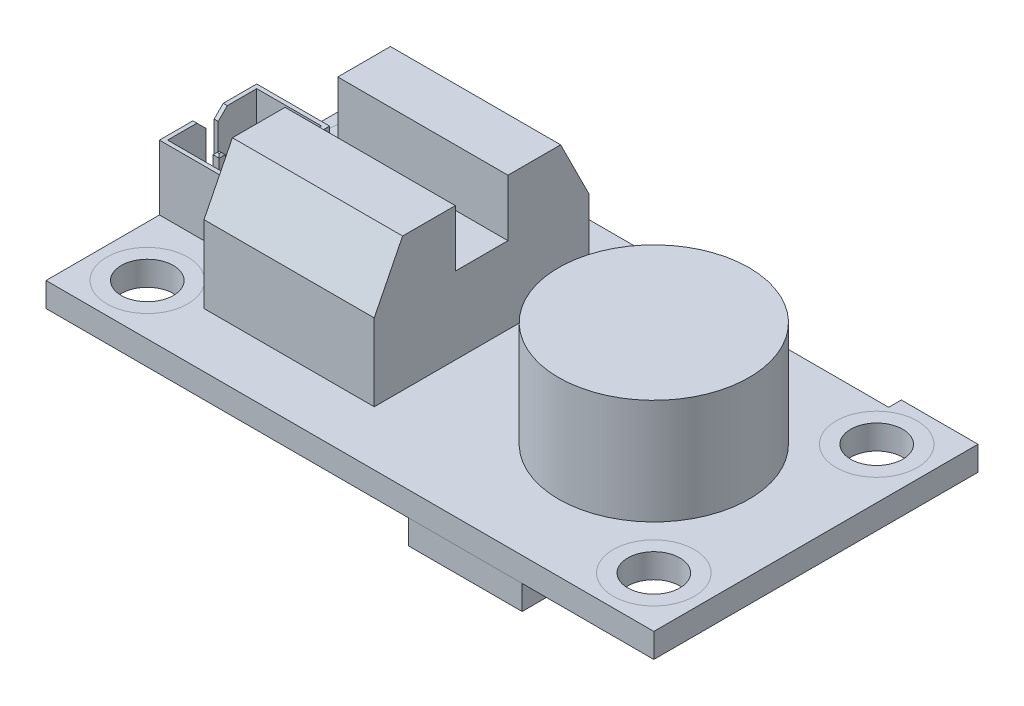
SolidWorks part; units mm, degrees
material "A-Glass Fiber"
ref_plane "Front Plane" through (0, 0, 0) normal (0, 0, 1) x (1, 0, 0)
ref_plane "Top Plane" through (0, 0, 0) normal (0, 1, 0) x (1, 0, 0)
ref_plane "Right Plane" through (0, 0, 0) normal (1, 0, 0) x (0, 0, -1)
sketch "Sketch1" plane through (0, 0, 0) normal (0, 1, 0) x (1, 0, 0)
  line L1 (19.05, -10.16) -> (-19.05, -10.16)
  line L2 (19.05, -10.16) -> (19.05, 10.16)
  line L3 (19.05, 10.16) -> (-19.05, 10.16)
  line L4 (-19.05, -10.16) -> (-19.05, 10.16)
  line L5 (19.05, -10.16) -> (-19.05, 10.16) construction
  line L6 (19.05, 10.16) -> (-19.05, -10.16) construction
  point P0 (0, 0)
  dimension "D1" = 38.1
  dimension "D2" = 20.32
extrude "Boss-Extrude1" add sketch "Sketch1" along normal blind 1.524
hole_wizard "#4 Clearance Hole1" positions "Sketch2" profile "Sketch3" hole size "#4" standard "ANSI Inch" end condition through all
sketch "Sketch2" plane through (0, 1.524, 0) normal (0, 1, 0) x (1, 0, 0)
  line L9 (-15.875, 6.985) -> (15.875, 6.985)
  line L10 (-15.875, 6.985) -> (-15.875, -6.985)
  line L11 (-15.875, -6.985) -> (15.875, -6.985)
  line L12 (15.875, 6.985) -> (15.875, -6.985)
  line L13 (19.05, -10.16) -> (19.05, 10.16) construction
  line L14 (19.05, 10.16) -> (-19.05, 10.16) construction
  line L15 (-19.05, 10.16) -> (-19.05, -10.16) construction
  line L16 (-19.05, -10.16) -> (19.05, -10.16) construction
  point P66 (-15.875, 6.985)
  point P67 (15.875, -6.985)
  point P70 (-15.875, -6.985)
  point P71 (15.875, 6.985)
  dimension "D1" = 3.175
  dimension "D2" = 3.175
  dimension "D3" = 3.175
  dimension "D4" = 3.175
sketch "Sketch3" plane through (-15.875, 1.524, -6.985) normal (1, 0, 0) x (0, 0, 1)
  line L0 (0, 0) -> (0, 1.524)
  line L1 (0, 1.524) -> (1.6319, 1.524)
  line L2 (1.6319, 1.524) -> (1.6319, 0)
  line L5 (1.6319, 0) -> (0, 0)
  line L11 (0, -6.35) -> (0, 107.95) construction
  dimension "Thru Hole Dia." = 3.2639
  dimension "Thru Hole Depth" = 1.524
sketch "Sketch4" plane through (0, 1.524, 0) normal (0, 1, 0) x (1, 0, 0)
  line L0 (-19.05, 10.16) -> (-19.05, -10.16) construction
  line L1 (-19.05, 3.048) -> (-14.478, 3.048)
  line L2 (-19.05, 3.048) -> (-19.05, -3.048)
  line L3 (-19.05, -3.048) -> (-14.478, -3.048)
  line L4 (-14.478, 3.048) -> (-14.478, -3.048)
  point P6 (-14.478, 0)
  dimension "D1" = 6.096
  dimension "D2" = 4.572
extrude "Boss-Extrude2" add sketch "Sketch4" along normal blind 4.064
sketch "Sketch5" plane through (0, 1.524, 0) normal (0, 1, 0) x (1, 0, 0)
  line L0 (19.05, -10.16) -> (19.05, 10.16) construction
  circle A0 centre (8.89, 0) radius 5.969
  dimension "D1" = 10.16
  dimension "D2" = 11.938
extrude "Boss-Extrude3" add sketch "Sketch5" along normal blind 6.604
sketch "Sketch6" plane through (0, 1.524, 0) normal (0, 1, 0) x (1, 0, 0)
  line L1 (-1.905, -6.731) -> (-12.573, -6.731)
  line L2 (-1.905, -6.731) -> (-1.905, 6.731)
  line L3 (-1.905, 6.731) -> (-12.573, 6.731)
  line L4 (-12.573, -6.731) -> (-12.573, 6.731)
  line L5 (-1.905, -6.731) -> (-12.573, 6.731) construction
  line L6 (-1.905, 6.731) -> (-12.573, -6.731) construction
  circle A1 centre (8.89, 0) radius 5.969 construction
  point P0 (-7.239, 0)
  dimension "D1" = 13.462
  dimension "D2" = 10.668
  dimension "D3" = 4.826
extrude "Boss-Extrude4" add sketch "Sketch6" along normal blind 4.826
sketch "Sketch7" plane through (-12.573, 0, 0) normal (-1, 0, 0) x (0, 0, 1)
  line L1 (-6.731, 6.35) -> (-4.953, 9.906)
  line L6 (0, 0) -> (0, 50000) construction
  line L18 (6.731, 6.35) -> (4.953, 9.906)
  line L19 (-4.953, 9.906) -> (-1.651, 9.906)
  line L20 (4.953, 9.906) -> (1.651, 9.906)
  line L21 (-1.651, 9.906) -> (-1.651, 6.35)
  line L22 (-6.731, 6.35) -> (6.731, 6.35) construction
  line L23 (1.651, 9.906) -> (1.651, 6.35)
  line L24 (-6.731, 6.35) -> (-1.651, 6.35)
  line L25 (6.731, 6.35) -> (1.651, 6.35)
  dimension "D1" = 3.556
  dimension "D2" = 3.302
  dimension "D3" = 3.302
extrude "Boss-Extrude5" add sketch "Sketch7" against normal up to surface (10.668 mm away) up to face at (-1.905, 3.937, 0)
sketch "Sketch8" plane through (0, 0, 0) normal (0, -1, 0) x (1, 0, 0)
  line L0 (19.05, -10.16) -> (-19.05, -10.16) construction
  line L1 (3.302, -10.16) -> (11.176, -10.16)
  line L2 (3.302, -10.16) -> (3.302, -4.572)
  line L3 (3.302, -4.572) -> (11.176, -4.572)
  line L4 (11.176, -10.16) -> (11.176, -4.572)
  line L5 (19.05, 10.16) -> (19.05, -10.16) construction
  dimension "D1" = 5.588
  dimension "D2" = 7.874
  dimension "D3" = 7.874
extrude "Boss-Extrude6" add sketch "Sketch8" along normal blind 3.048
sketch "Sketch9" plane through (0, 0, 0) normal (0, -1, 0) x (1, 0, 0)
  line L0 (-19.05, 10.16) -> (19.05, 10.16) construction
  line L1 (3.683, 10.16) -> (10.795, 10.16)
  line L2 (3.683, 10.16) -> (3.683, 5.08)
  line L3 (3.683, 5.08) -> (10.795, 5.08)
  line L4 (10.795, 10.16) -> (10.795, 5.08)
  line L5 (11.176, -4.572) -> (3.302, -4.572) construction
  point P8 (7.239, -4.572)
  point P9 (7.239, 5.08)
  dimension "D1" = 5.08
  dimension "D2" = 7.112
extrude "Boss-Extrude7" add sketch "Sketch9" along normal blind 1.524
sketch "Sketch10" plane through (0, 0, 0) normal (0, -1, 0) x (1, 0, 0)
  line L0 (10.795, 5.08) -> (10.795, 10.16) construction
  line L1 (14.859, 2.032) -> (12.319, 2.032)
  line L2 (14.859, 2.032) -> (14.859, -2.032)
  line L3 (14.859, -2.032) -> (12.319, -2.032)
  line L4 (12.319, 2.032) -> (12.319, -2.032)
  point P4 (14.859, 0)
  dimension "D1" = 4.064
  dimension "D2" = 2.54
  dimension "D3" = 1.524
extrude "Boss-Extrude8" add sketch "Sketch10" along normal blind 1.016
sketch "Sketch11" plane through (0, 0, 0) normal (0, -1, 0) x (1, 0, 0)
  line L0 (3.683, 10.16) -> (3.683, 5.08) construction
  line L1 (1.651, -2.54) -> (6.731, -2.54)
  line L2 (1.651, -2.54) -> (1.651, 2.54)
  line L3 (1.651, 2.54) -> (6.731, 2.54)
  line L4 (6.731, -2.54) -> (6.731, 2.54)
  line L5 (1.651, -2.54) -> (6.731, 2.54) construction
  line L6 (1.651, 2.54) -> (6.731, -2.54) construction
  point P0 (4.191, 0)
  dimension "D1" = 5.08
  dimension "D2" = 2.032
extrude "Boss-Extrude9" add sketch "Sketch11" along normal blind 1.016
sketch "Sketch12" plane through (0, 0, 0) normal (0, -1, 0) x (1, 0, 0)
  line L0 (-19.05, 10.16) -> (3.683, 10.16) construction
  line L1 (-0.381, 6.096) -> (-4.445, 6.096)
  line L2 (-0.381, 6.096) -> (-0.381, 8.128)
  line L3 (-0.381, 8.128) -> (-4.445, 8.128)
  line L4 (-4.445, 6.096) -> (-4.445, 8.128)
  line L5 (-0.381, 6.096) -> (-4.445, 8.128) construction
  line L6 (-0.381, 8.128) -> (-4.445, 6.096) construction
  line L7 (3.683, 10.16) -> (3.683, 5.08) construction
  point P0 (-2.413, 7.112)
  dimension "D1" = 2.032
  dimension "D2" = 4.064
  dimension "D3" = 2.032
  dimension "D4" = 4.064
extrude "Boss-Extrude10" add sketch "Sketch12" along normal blind 1.016
sketch "Sketch13" plane through (0, 0, 0) normal (0, -1, 0) x (1, 0, 0)
  line L0 (3.302, -4.572) -> (3.302, -10.16) construction
  line L1 (-2.286, -7.62) -> (-5.334, -7.62)
  line L2 (-2.286, -7.62) -> (-2.286, -4.572)
  line L3 (-2.286, -4.572) -> (-5.334, -4.572)
  line L4 (-5.334, -7.62) -> (-5.334, -4.572)
  line L5 (-2.286, -7.62) -> (-5.334, -4.572) construction
  line L6 (-2.286, -4.572) -> (-5.334, -7.62) construction
  line L7 (3.302, -10.16) -> (-19.05, -10.16) construction
  point P0 (-3.81, -6.096)
  dimension "D1" = 3.048
  dimension "D2" = 5.588
  dimension "D3" = 2.54
extrude "Boss-Extrude11" add sketch "Sketch13" along normal blind 0.508
sketch "Sketch14" plane through (0, 0, 0) normal (0, -1, 0) x (1, 0, 0)
  line L0 (-19.05, -10.16) -> (-19.05, 10.16) construction
  line L1 (-11.43, -4.572) -> (-8.382, -4.572)
  line L2 (-11.43, -4.572) -> (-11.43, -8.128)
  line L3 (-11.43, -8.128) -> (-8.382, -8.128)
  line L4 (-8.382, -4.572) -> (-8.382, -8.128)
  line L5 (-11.43, -4.572) -> (-8.382, -8.128) construction
  line L6 (-11.43, -8.128) -> (-8.382, -4.572) construction
  line L7 (3.302, -10.16) -> (-19.05, -10.16) construction
  point P0 (-9.906, -6.35)
  dimension "D1" = 3.556
  dimension "D2" = 3.048
  dimension "D3" = 7.62
  dimension "D4" = 2.032
extrude "Boss-Extrude12" add sketch "Sketch14" along normal blind 1.016
sketch "Sketch15" plane through (0, 0, 0) normal (0, -1, 0) x (1, 0, 0)
  line L0 (3.302, -10.16) -> (-19.05, -10.16) construction
  line L1 (-16.51, 3.302) -> (-14.478, 3.302)
  line L2 (-16.51, 3.302) -> (-16.51, -0.762)
  line L3 (-16.51, -0.762) -> (-14.478, -0.762)
  line L4 (-14.478, 3.302) -> (-14.478, -0.762)
  line L5 (-16.51, 3.302) -> (-14.478, -0.762) construction
  line L6 (-16.51, -0.762) -> (-14.478, 3.302) construction
  line L7 (-19.05, -10.16) -> (-19.05, 10.16) construction
  point P0 (-15.494, 1.27)
  dimension "D1" = 4.064
  dimension "D2" = 2.032
  dimension "D3" = 9.398
  dimension "D4" = 2.54
extrude "Boss-Extrude13" add sketch "Sketch15" along normal blind 1.524
sketch "Sketch16" plane through (0, 0, 0) normal (0, -1, 0) x (1, 0, 0)
  line L0 (-19.05, -10.16) -> (-19.05, 10.16) construction
  line L1 (-7.874, -1.524) -> (-10.922, -1.524)
  line L2 (-7.874, -1.524) -> (-7.874, 1.524)
  line L3 (-7.874, 1.524) -> (-10.922, 1.524)
  line L4 (-10.922, -1.524) -> (-10.922, 1.524)
  line L5 (-7.874, -1.524) -> (-10.922, 1.524) construction
  line L6 (-7.874, 1.524) -> (-10.922, -1.524) construction
  point P0 (-9.398, 0)
  point P8 (-19.05, 0)
  dimension "D1" = 3.048
  dimension "D2" = 8.128
extrude "Boss-Extrude14" add sketch "Sketch16" along normal blind 1.016
sketch "Sketch17" plane through (0, 0, 0) normal (0, -1, 0) x (1, 0, 0)
  line L0 (-19.05, -10.16) -> (-19.05, 10.16) construction
  line L1 (3.302, -10.16) -> (-19.05, -10.16) construction
  circle A0 centre (-11.684, -3.556) radius 0.508
  dimension "D1" = 1.016
  dimension "D2" = 6.858
  dimension "D3" = 6.096
extrude "Boss-Extrude15" add sketch "Sketch17" along normal blind 1.524
pattern_linear "LPattern1" count 4 spacing 2.794 along (1, 0, 0) of "Boss-Extrude15"
mirror "Mirror1" about plane through (0, 0, 0) normal (0, 0, 1) of "LPattern1"
sketch "Sketch22" plane through (0, 1.524, 0) normal (0, 1, 0) x (1, 0, 0)
  line L0 (19.05, 10.16) -> (-19.05, 10.16) construction
  line L1 (0.635, 10.16) -> (14.2431, 10.16)
  line L2 (0.635, 10.16) -> (0.635, 9.3663)
  line L3 (0.635, 9.3663) -> (14.2431, 9.3663)
  line L4 (14.2431, 10.16) -> (14.2431, 9.3663)
  line L5 (-1.905, 6.731) -> (-1.905, 4.953) construction
  circle A0 centre (15.875, 6.985) radius 1.6319 construction
  dimension "D1" = 0.7937
  dimension "D2" = 2.54
extrude "Cut-Extrude2" cut sketch "Sketch22" against normal up to surface (1.524 mm away) up to face at (-3.302, 0, 4.064)
sketch "Sketch18" plane through (-19.05, 0, 0) normal (-1, 0, 0) x (0, 0, 1)
  line L0 (-3.048, 1.524) -> (3.048, 1.524)
split line "Split Line1"
sketch "Sketch19" plane through (0, 0, 10.16) normal (0, 0, 1) x (1, 0, 0)
  line L0 (3.683, 0) -> (10.795, 0)
  line L1 (11.176, 0) -> (3.302, 0) construction
  line L2 (10.795, 0) -> (19.05, 0) construction
split line "Split Line2"
sketch "Sketch23" plane through (0, 1.524, 0) normal (0, 1, 0) x (1, 0, 0)
  circle A0 centre (-15.875, 6.985) radius 2.54
  circle A1 centre (15.875, 6.985) radius 2.54
  circle A2 centre (15.875, -6.985) radius 2.54
  circle A3 centre (-15.875, -6.985) radius 2.54
  dimension "D1" = 5.08
split line "Split Line3"
sketch "Sketch24" plane through (0, 5.588, 0) normal (0, 1, 0) x (1, 0, 0)
  line L8 (-18.796, 2.794) -> (-18.796, -2.794)
  line L9 (-18.796, -2.794) -> (-14.732, -2.794)
  line L10 (-14.732, -2.794) -> (-14.732, 2.794)
  line L11 (-14.732, 2.794) -> (-18.796, 2.794)
  line L12 (-18.796, 2.794) -> (-18.796, -2.794)
  line L13 (-18.796, -2.794) -> (-14.732, -2.794)
  line L14 (-14.732, -2.794) -> (-14.732, 2.794)
  line L15 (-14.732, 2.794) -> (-18.796, 2.794)
  dimension "D1" = 0.254
extrude "Cut-Extrude3" cut sketch "Sketch24" against normal offset from surface (3.556 mm away) 0.508 contours L12 L13 L14 L15 up to face at (15.875, 1.524, 9.525)
sketch "Sketch25" plane through (0, 2.032, 0) normal (0, 1, 0) x (1, 0, 0)
  line L0 (-17.018, 2.794) -> (-17.018, -2.794) construction
  line L1 (-14.732, 2.794) -> (-18.796, 2.794) construction
  line L2 (-14.732, -2.794) -> (-18.796, -2.794) construction
  line L3 (-18.796, 2.794) -> (-18.796, -2.794) construction
  line L4 (-17.018, 0) -> (-18.796, 0) construction
  line L5 (-16.8275, 1.143) -> (-17.2085, 1.143)
  line L6 (-16.8275, 1.143) -> (-16.8275, 1.524)
  line L7 (-16.8275, 1.524) -> (-17.2085, 1.524)
  line L8 (-17.2085, 1.143) -> (-17.2085, 1.524)
  line L9 (-16.8275, 1.143) -> (-17.2085, 1.524) construction
  line L10 (-16.8275, 1.524) -> (-17.2085, 1.143) construction
  line L11 (-16.8275, -1.524) -> (-17.2085, -1.524)
  line L12 (-16.8275, -1.524) -> (-16.8275, -1.143)
  line L13 (-16.8275, -1.143) -> (-17.2085, -1.143)
  line L14 (-17.2085, -1.524) -> (-17.2085, -1.143)
  line L15 (-16.8275, -1.524) -> (-17.2085, -1.143) construction
  line L16 (-16.8275, -1.143) -> (-17.2085, -1.524) construction
  line L17 (-18.796, -2.794) -> (-18.796, 2.794) construction
  point P8 (-17.018, 1.3335)
  point P13 (-17.018, -1.3335)
  dimension "D1" = 1.778
  dimension "D2" = 0.381
  dimension "D3" = 1.143
  dimension "D4" = 1.143
extrude "Boss-Extrude16" add sketch "Sketch25" along normal offset from surface (3.048 mm away) 0.508 up to face at (-16.764, 5.588, 0)
chamfer "Chamfer1" distance 0.127 angle 45 8 edges at (-16.8275, 5.08, 1.3335) (-17.018, 5.08, 1.524) (-17.2085, 5.08, 1.3335) (-17.018, 5.08, 1.143) (-16.8275, 5.08, -1.3335) (-17.018, 5.08, -1.143) (-17.2085, 5.08, -1.3335) (-17.018, 5.08, -1.524)
sketch "Sketch26" plane through (-19.05, 0, 0) normal (-1, 0, 0) x (0, 0, 1)
  line L0 (0, 5.588) -> (0, 1.524) construction
  line L1 (-3.048, 5.588) -> (3.048, 5.588) construction
  line L2 (-3.048, 1.524) -> (3.048, 1.524) construction
  line L3 (-0.9525, 5.588) -> (-0.381, 5.0165)
  line L4 (0.9525, 5.588) -> (0.381, 5.0165)
  line L5 (-0.381, 5.0165) -> (-0.381, 2.286)
  line L6 (0.381, 5.0165) -> (0.381, 2.286)
  line L7 (-0.381, 2.286) -> (0.381, 2.286)
  line L8 (-0.9525, 5.588) -> (0.9525, 5.588)
  point P12 (0, 2.286)
  dimension "D1" = 0.762
  dimension "D2" = 135
  dimension "D3" = 1.905
  dimension "D4" = 0.762
extrude "Cut-Extrude4" cut sketch "Sketch26" against normal up to surface (0.254 mm away) up to face at (-18.796, 3.81, 0)
chamfer "Chamfer2" distance 1.778 angle 57 2 edges at (3.302, -3.048, -7.366) (11.176, -3.048, -7.366) first distance on face at (3.302, -1.2192, -7.7661) first distance on face at (11.176, -1.2192, -7.7661)
